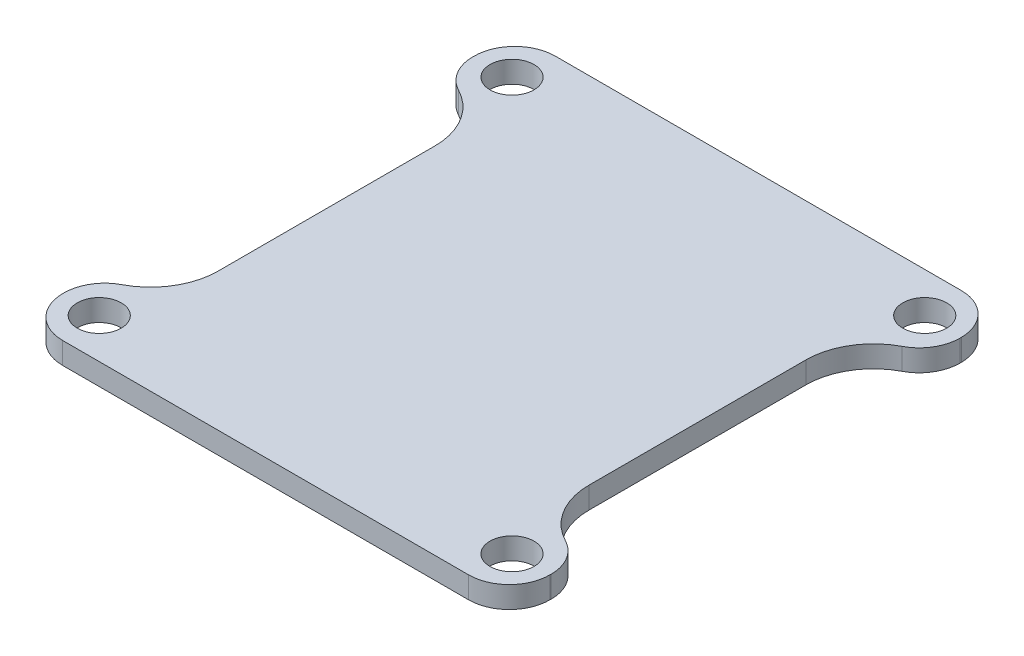
SolidWorks part; units mm, degrees
ref_plane "Front Plane" through (0, 0, 0) normal (0, 0, 1) x (1, 0, 0)
ref_plane "Top Plane" through (0, 0, 0) normal (0, 1, 0) x (1, 0, 0)
ref_plane "Right Plane" through (0, 0, 0) normal (1, 0, 0) x (0, 0, -1)
sketch "Sketch1" plane through (0, 0, 0) normal (0, 1, 0) x (1, 0, 0)
  line L0 (0, 18.2) -> (0, -18.2) construction
  line L1 (-18, 18.2) -> (18, 18.2)
  line L2 (-18, 18.2) -> (-18, -18.2)
  line L3 (-18, -18.2) -> (18, -18.2)
  line L4 (18, 18.2) -> (18, -18.2)
  line L5 (-18, 18.2) -> (18, -18.2) construction
  line L6 (-18, -18.2) -> (18, 18.2) construction
  line L7 (13.7, 18.2) -> (-13.7, 18.2)
  line L8 (13.7, 18.2) -> (13.7, -18.2)
  line L9 (13.7, -18.2) -> (-13.7, -18.2)
  line L10 (-13.7, 18.2) -> (-13.7, -18.2)
  line L11 (13.7, 18.2) -> (-13.7, -18.2) construction
  line L12 (13.7, -18.2) -> (-13.7, 18.2) construction
  line L13 (-18, 0) -> (18, 0) construction
  line L15 (18, 12.1) -> (-18, 12.1)
  line L16 (18, 12.1) -> (18, -12.1)
  line L17 (18, -12.1) -> (-18, -12.1)
  line L18 (-18, 12.1) -> (-18, -12.1)
  line L19 (18, 12.1) -> (-18, -12.1) construction
  line L20 (18, -12.1) -> (-18, 12.1) construction
  circle A0 centre (-15.25, 15.25) radius 1.625
  circle A1 centre (15.25, 15.25) radius 1.625
  circle A2 centre (15.25, -15.25) radius 1.625
  circle A3 centre (-15.25, -15.25) radius 1.625
  point P0 (0, 0)
  point P5 (0, 0)
  point P23 (0, 0)
  dimension "D4" = 3.25
  dimension "D1" = 36.4
  dimension "D2" = 36
  dimension "D3" = 27.4
  dimension "D5" = 30.5
  dimension "D6" = 30.5
  dimension "D7" = 24.2
extrude "Boss-Extrude1" add sketch "Sketch1" along normal blind 1.6 contours L15 L8 L1 L10 | L17 L8 L15 L10 | L4 L17 L8 L3 A2 | L8 L17 L10 L3 | L10 L17 L2 L3 A3 | L15 L4 L1 L8 A1 | L15 L10 L1 L2 A0 region at (-15.85, 0, -18.1254) region at (0, 0, -15.1499) region at (15.85, 0, -18.1254) region at (-15.85, 0, 12.1746) region at (0, 0, 0) region at (0, 0, 15.1499) region at (15.85, 0, 12.1746)
fillet "Fillet1" radius 3 8 edges at (-18, 0.8, 12.1) (-18, 0.8, -12.1) (18, 0.8, -12.1) (18, 0.8, 12.1) (18, 0.8, 18.2) (-18, 0.8, 18.2) (-18, 0.8, -18.2) (18, 0.8, -18.2)
fillet "Fillet2" radius 5 4 edges at (13.7, 0.8, -12.1) (13.7, 0.8, 12.1) (-13.7, 0.8, 12.1) (-13.7, 0.8, -12.1)
